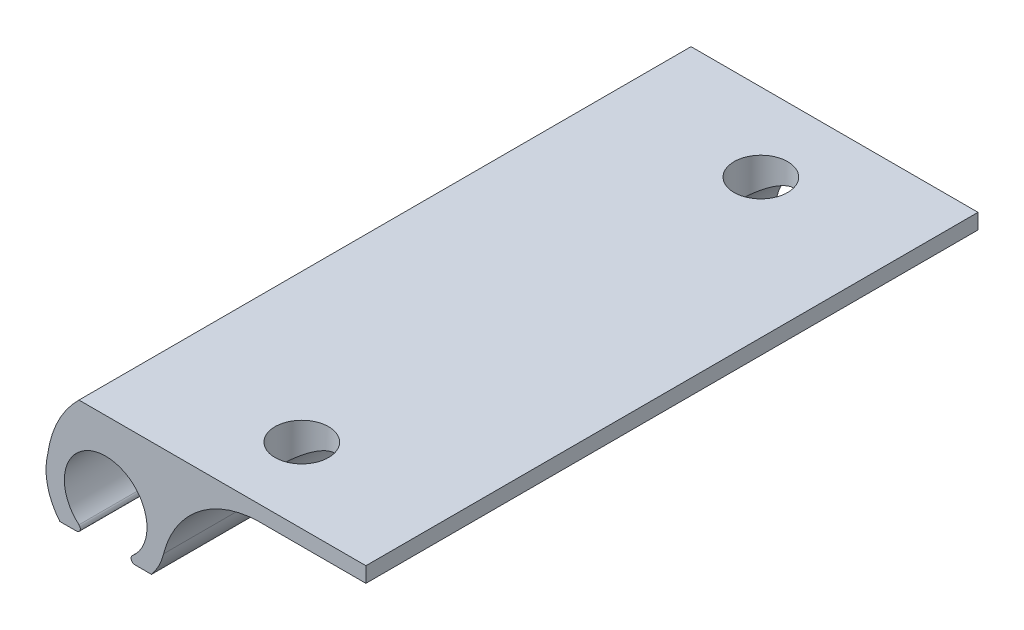
SolidWorks part; units mm, degrees
ref_plane "Front Plane" through (0, 0, 0) normal (0, 0, 1) x (1, 0, 0)
ref_plane "Top Plane" through (0, 0, 0) normal (0, 1, 0) x (1, 0, 0)
ref_plane "Right Plane" through (0, 0, 0) normal (1, 0, 0) x (0, 0, -1)
ref_plane "Плоскость1" through (0, -4, 0) normal (0, 1, 0) x (1, 0, 0)
sketch "Эскиз1" plane through (0, 0, 0) normal (0, 1, 0) x (1, 0, 0)
  line L0 (-40.6, -27.2) -> (40.6, -27.2)
  line L1 (0, 0) -> (44.6, 0) construction
  line L6 (40.6, 27.2) -> (40.6, 23.2) construction
  line L7 (40.6, 27.2) -> (-40.6, 27.2)
  line L11 (-40.6, 27.2) -> (-40.6, 23.2) construction
  line L20 (-44.6, 23.2) -> (-44.6, -23.2)
  line L24 (44.6, -23.2) -> (44.6, 23.2)
  line L51 (-5.4, 27.2) -> (33.6, 27.2)
  arc A0 (-40.6, 27.2) -> (-44.6, 23.2) centre (-40.6, 23.2) ccw
  arc A1 (44.6, 23.2) -> (40.6, 27.2) centre (40.6, 23.2) ccw
  arc A2 (-44.6, -23.2) -> (-40.6, -27.2) centre (-40.6, -23.2) ccw
  arc A3 (40.6, -27.2) -> (44.6, -23.2) centre (40.6, -23.2) ccw
  point P37 (0, 0)
  point P42 (0, 0)
extrude "Бобышка-Вытянуть1" add sketch "Эскиз1" along normal blind 3.9 contours A3 L24 A1 L7 A0 L20 A2 L0 region at (0, 0, 0)
sketch "Эскиз2" plane through (0, -4, 0) normal (0, 1, 0) x (1, 0, 0)
  line L0 (0, 0) -> (0, 45) construction
  line L1 (-45, 45) -> (45, 45) construction
  line L2 (-44.3008, 45) -> (-45, 45) construction
  line L3 (-45, 45) -> (-45, -45) construction
  line L4 (-45, -45) -> (45, -45) construction
  line L5 (45, -45) -> (45, 45) construction
  line L6 (-45, 0) -> (0, 0) construction
  dimension "D1" = 90
  dimension "D2" = 45
  dimension "D3" = 90
  dimension "D4" = 45
sketch "Эскиз3" plane through (0, 0, 0) normal (0, 0, 1) x (1, 0, 0)
  line L0 (-45, -4) -> (45, -4) construction
  line L1 (-45, -4) -> (45, -4) construction
  line L2 (-44.8219, -4) -> (-44.8219, -6.4999) construction
  line L5 (-47.8153, -6.4999) -> (-45.8419, -6.4999)
  line L7 (-43.8019, -6.4999) -> (-41.8285, -6.4999)
  arc A0 (-43.8019, -6.4999) -> (-45.8419, -6.4999) centre (-44.8219, -4) ccw
  arc A1 (-41.8285, -6.4999) -> (-47.8153, -6.4999) centre (-44.8219, -4) ccw
  point P7 (-45.8419, -6.4999)
  point P9 (-43.8019, -6.4999)
  dimension "D1" = 5.4
  dimension "D2" = 7.8
  dimension "D4" = 45
  dimension "D3" = 2.04
  dimension "D5" = 2.9934
  dimension "D6" = 2.4999
extrude "Бобышка-Вытянуть3" add sketch "Эскиз3" along normal mid plane 40
sketch "Эскиз5" plane through (0, 0, 0) normal (0, 0, 1) x (1, 0, 0)
  line L1 (-41.6689, 3.0157) -> (-41.6318, 2.9999)
  line L8 (-45, -4) -> (45, -4) construction
  line L9 (-48.6038, -4.9525) -> (-47.3483, -4.9525)
  line L10 (-42.2954, -4.9525) -> (-41.04, -4.9525)
  line L11 (-36.6416, 0.871) -> (-34.6, 0)
  arc A2 (-42.2954, -4.9525) -> (-47.3483, -4.9525) centre (-44.8219, -4) ccw
  arc A6 (-34.6, 0) -> (-41.04, -4.9525) centre (-34.7077, -6.5233) ccw
  arc A8 (-36.6416, 0.871) -> (-48.6038, -4.9525) centre (-41.6689, -4) ccw
  arc A9 (-43.8019, -6.4999) -> (-45.8419, -6.4999) centre (-44.8219, -4) ccw construction
  arc A10 (-41.8285, -6.4999) -> (-47.8153, -6.4999) centre (-44.8219, -4) ccw construction
  point P6 (0, 0)
  point P15 (0, 0)
  dimension "D1" = 7
  dimension "D2" = 6.5242
  dimension "D3" = 34.7077
  dimension "D4" = 36.6416
extrude "Бобышка-Вытянуть5" add sketch "Эскиз5" along normal mid plane 40 contours L11 A8 L9 A2 L10 A6 region at (-42.3833, -0.3298, 0)
fillet "Скругление1" radius 0.25 2 edges at (-43.8019, -6.4999, 0) (-45.8419, -6.4999, 0)
mirror "Зеркальное отражение1" about plane through (0, 0, 0) normal (1, 0, 0) of "Бобышка-Вытянуть5"
mirror "Зеркальное отражение2" about plane through (0, 0, 0) normal (1, 0, 0) of "Скругление1", "Бобышка-Вытянуть3"
sketch "Эскиз7" plane through (0, 0, 20) normal (0, 0, 1) x (1, 0, 0)
  line L0 (-45, -4) -> (45, -4) construction
  line L1 (49.5, -4) -> (-49.5, -4) construction
  circle A0 centre (-45, -4) radius 5.5
  dimension "D1" = 11
extrude "Вырез-Вытянуть3" cut sketch "Эскиз7" along normal through all
mirror "Зеркальное отражение3" about plane through (0, 0, 0) normal (1, 0, 0) of "Вырез-Вытянуть3" second plane through (0, 0, 0) second plane normal (0, 0, 1)
sketch "Esquisse1" plane through (0, 3.9, 0) normal (0, 1, 0) x (1, 0, 0)
  line L0 (0, 0) -> (0, 45) construction
  line L1 (-44.6, 20) -> (0, 20)
  line L2 (-44.6, 20) -> (-44.6, -20)
  line L3 (-44.6, -20) -> (0, -20)
  line L4 (0, 20) -> (0, -20)
  point P7 (0, 0)
extrude "Enlèv. mat.-Extru.1" cut sketch "Esquisse1" against normal blind 1.54
sketch "Esquisse2" plane through (0, 3.9, 0) normal (0, 1, 0) x (1, 0, 0)
  line L0 (-44.6, 20) -> (-44.6, 27.2)
  line L1 (-44.6, 27.2) -> (51.6, 27.2)
  line L2 (51.6, 27.2) -> (51.6, -27.2)
  line L3 (51.6, -27.2) -> (-44.6, -27.2)
  line L4 (-44.6, -27.2) -> (-44.6, -20)
  line L5 (-44.6, -20) -> (0, -20)
  line L6 (0, -20) -> (0, 20)
  line L7 (0, 20) -> (-44.6, 20)
  line L8 (-40.6, -27.2) -> (40.6, -27.2) construction
  line L10 (40.6, 27.2) -> (-40.6, 27.2) construction
  line L11 (44.6, -23.2) -> (44.6, 23.2) construction
  dimension "D1" = 7
extrude "Enlèv. mat.-Extru.2" cut sketch "Esquisse2" against normal through all
sketch "Esquisse3" plane through (0, 0, 20) normal (0, 0, 1) x (1, 0, 0)
  line L0 (0, 0) -> (0, 2.36) construction
  line L1 (-50, 2.36) -> (0, 2.36)
  line L2 (-50, 2.36) -> (-50, 1)
  line L3 (-50, 1) -> (0, 1)
  line L4 (0, 2.36) -> (0, 1)
  line L5 (0, 0) -> (-34.8154, 0) construction
  line L6 (-44.6, 2.36) -> (0, 2.36) construction
  point P13 (-50, 1.68)
  dimension "D2" = 50
  dimension "D1" = 1
extrude "Enlèv. mat.-Extru.3" cut sketch "Esquisse3" against normal through all
sketch "Esquisse4" plane through (0, 0, 0) normal (0, -1, 0) x (1, 0, 0)
  line L0 (-27.8154, 20) -> (-27.8154, -20)
  line L1 (-27.8154, 20) -> (0, 20)
  line L3 (-27.8154, -20) -> (0, -20)
  line L4 (0, 20) -> (0, -20)
  line L9 (0, 20) -> (-34.8154, 20) construction
  line L10 (-34.8154, -20) -> (0, -20) construction
  line L11 (0, -20) -> (0, 20) construction
  line L12 (-34.8154, 20) -> (-34.8154, -20) construction
  dimension "D1" = 7
extrude "Enlèv. mat.-Extru.4" cut sketch "Esquisse4" against normal through all
sketch "Esquisse5" plane through (0, 1, 0) normal (0, 1, 0) x (1, 0, 0)
  line L0 (-46.5679, 20) -> (-27.8154, 20) construction
  line L1 (-27.8154, -20) -> (-27.8154, 20) construction
  line L2 (-46.5679, -20) -> (-27.8154, -20) construction
  circle A0 centre (-36.9054, 14.9) radius 1.75
  circle A1 centre (-36.9054, -15.1) radius 1.75
  dimension "D1" = 3.5
  dimension "D2" = 3.5
  dimension "D3" = 5.1
  dimension "D4" = 9.09
  dimension "D5" = 9.09
  dimension "D6" = 4.9
extrude "Enlèv. mat.-Extru.5" cut sketch "Esquisse5" against normal through all
